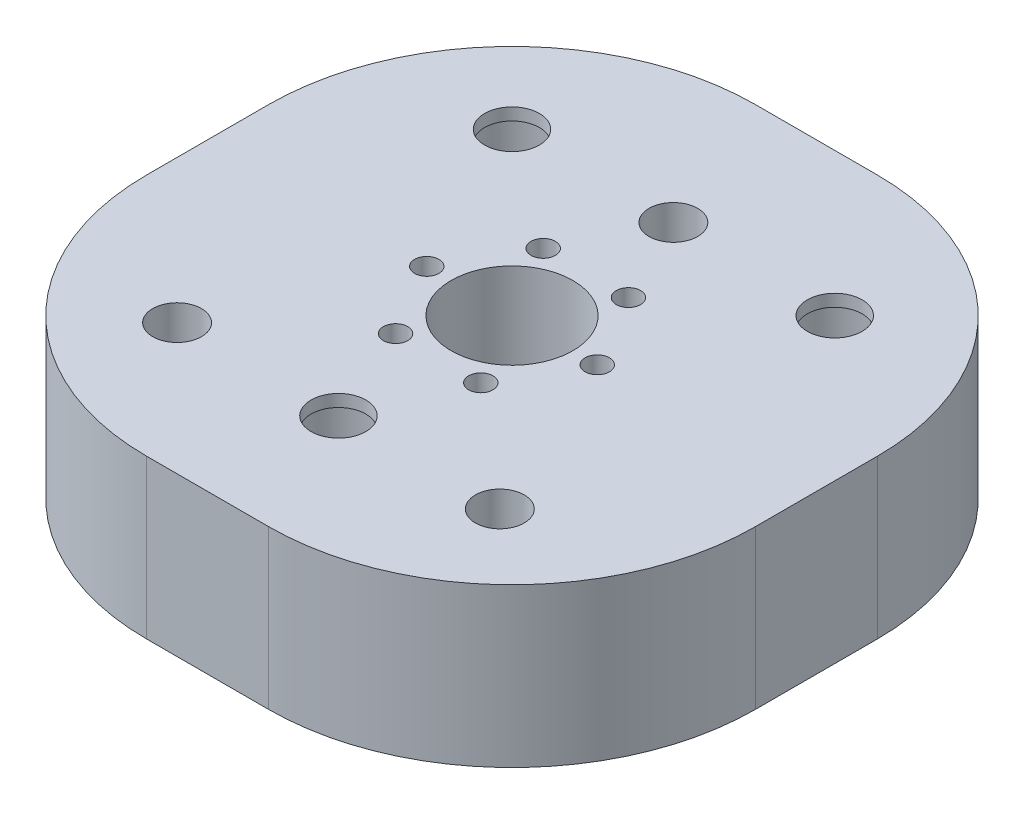
SolidWorks part; units mm, degrees
ref_plane "Front Plane" through (0, 0, 0) normal (0, 0, 1) x (1, 0, 0)
ref_plane "Top Plane" through (0, 0, 0) normal (0, 1, 0) x (1, 0, 0)
ref_plane "Right Plane" through (0, 0, 0) normal (1, 0, 0) x (0, 0, -1)
sketch "Sketch1" plane through (0, 0, 0) normal (0, 1, 0) x (1, 0, 0)
  line L5 (-50, -50) -> (50, -50)
  line L6 (-50, -50) -> (-50, 50)
  line L7 (-50, 50) -> (50, 50)
  line L8 (50, -50) -> (50, 50)
  line L9 (-50, -50) -> (50, 50) construction
  line L10 (-50, 50) -> (50, -50) construction
  circle A0 centre (0, 0) radius 10
  point P0 (0, 0)
  dimension "D3" = 20
  dimension "D1" = 100
  dimension "D2" = 100
extrude "Boss-Extrude1" add sketch "Sketch1" along normal blind 26
sketch "Sketch2" plane through (0, 0, 0) normal (0, -1, 0) x (1, 0, 0)
  circle A0 centre (0, 0) radius 18
  dimension "D1" = 36
extrude "Cut-Extrude1" cut sketch "Sketch2" against normal blind 10
sketch "Sketch3" plane through (0, 0, 0) normal (0, -1, 0) x (1, 0, 0)
  circle A0 centre (0, 28.5) radius 7.55
  circle A1 centre (26.5, -26.5) radius 7.55
  circle A2 centre (-26.5, -26.5) radius 7.55
  dimension "D1" = 15.1
extrude "Cut-Extrude2" cut sketch "Sketch3" against normal blind 24
sketch "Sketch4" plane through (0, 0, 0) normal (0, -1, 0) x (1, 0, 0)
  circle A0 centre (0, 28.5) radius 4.5
  circle A1 centre (26.5, -26.5) radius 4.5
  circle A2 centre (-26.5, -26.5) radius 4.5
  dimension "D1" = 9
extrude "Cut-Extrude3" cut sketch "Sketch4" against normal through all both and the other way through all
sketch "Sketch6" plane through (0, 26, 0) normal (0, 1, 0) x (1, 0, 0)
  arc A0 (8, 13.8564) -> (6, 10.3923) centre (7, 12.1244) ccw construction
  arc A1 (6, 10.3923) -> (8, 13.8564) centre (7, 12.1244) ccw construction
  arc A2 (16, 0) -> (12, 0) centre (14, 0) ccw construction
  arc A3 (12, 0) -> (16, 0) centre (14, 0) ccw construction
  arc A4 (8, -13.8564) -> (6, -10.3923) centre (7, -12.1244) ccw construction
  arc A5 (6, -10.3923) -> (8, -13.8564) centre (7, -12.1244) ccw construction
  arc A6 (-8, -13.8564) -> (-6, -10.3923) centre (-7, -12.1244) ccw construction
  arc A7 (-6, -10.3923) -> (-8, -13.8564) centre (-7, -12.1244) ccw construction
  arc A8 (-12, 0) -> (-16, 0) centre (-14, 0) ccw construction
  arc A9 (-16, 0) -> (-12, 0) centre (-14, 0) ccw construction
  arc A10 (-6, 10.3923) -> (-8, 13.8564) centre (-7, 12.1244) ccw construction
  arc A11 (-8, 13.8564) -> (-6, 10.3923) centre (-7, 12.1244) ccw construction
  arc A12 (8, 13.8564) -> (6, 10.3923) centre (7, 12.1244) ccw
  arc A13 (6, 10.3923) -> (8, 13.8564) centre (7, 12.1244) ccw
  arc A14 (16, 0) -> (12, 0) centre (14, 0) ccw
  arc A15 (12, 0) -> (16, 0) centre (14, 0) ccw
  arc A16 (8, -13.8564) -> (6, -10.3923) centre (7, -12.1244) ccw
  arc A17 (6, -10.3923) -> (8, -13.8564) centre (7, -12.1244) ccw
  arc A18 (-8, -13.8564) -> (-6, -10.3923) centre (-7, -12.1244) ccw
  arc A19 (-6, -10.3923) -> (-8, -13.8564) centre (-7, -12.1244) ccw
  arc A20 (-12, 0) -> (-16, 0) centre (-14, 0) ccw
  arc A21 (-16, 0) -> (-12, 0) centre (-14, 0) ccw
  arc A22 (-6, 10.3923) -> (-8, 13.8564) centre (-7, 12.1244) ccw
  arc A23 (-8, 13.8564) -> (-6, 10.3923) centre (-7, 12.1244) ccw
extrude "Cut-Extrude4" cut sketch "Sketch6" against normal through all both
sketch "Sketch8" plane through (0, 26, 0) normal (0, 1, 0) x (1, 0, 0)
  line L0 (-26.5, -28.5) -> (26.5, -28.5) construction
  circle A0 centre (-26.5, -28.5) radius 4.005
  circle A1 centre (26.5, -28.5) radius 4.005
  circle A2 centre (0, 26.5) radius 4.005
  point P6 (0, -28.5)
  dimension "D1" = 8.01
extrude "Cut-Extrude5" cut sketch "Sketch8" against normal offset from surface (23 mm away) 3 up to face at (0, 0, 20.95)
fillet "Fillet1" radius 40 4 edges at (50, 13, 50) (50, 13, -50) (-50, 13, -50) (-50, 13, 50)
